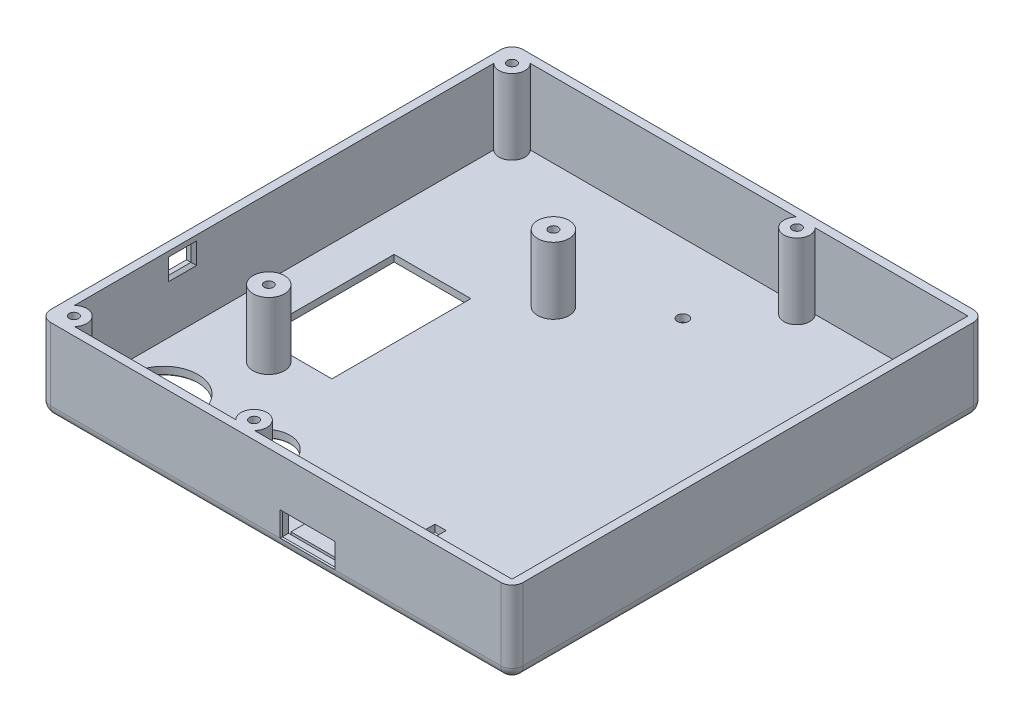
SolidWorks part; units mm, degrees
material "PLA"
ref_plane "前视基准面" through (0, 0, 0) normal (0, 0, 1) x (1, 0, 0)
ref_plane "上视基准面" through (0, 0, 0) normal (0, 1, 0) x (1, 0, 0)
ref_plane "右视基准面" through (0, 0, 0) normal (1, 0, 0) x (0, 0, -1)
sketch "草图1" plane through (0, 0, 0) normal (0, 1, 0) x (1, 0, 0)
  line L1 (-42.5, 42.5) -> (42.5, 42.5)
  line L2 (-42.5, 42.5) -> (-42.5, -42.5)
  line L3 (-42.5, -42.5) -> (42.5, -42.5)
  line L4 (42.5, 42.5) -> (42.5, -42.5)
  line L5 (-42.5, 42.5) -> (42.5, -42.5) construction
  line L6 (-42.5, -42.5) -> (42.5, 42.5) construction
  point P0 (0, 0)
  dimension "D1" = 85
  dimension "D2" = 85
extrude "凸台-拉伸1" add sketch "草图1" along normal blind 15
shell "抽壳1" thickness 1.5 removed face at (0, 15, 0)
fillet "圆角1" radius 2 4 edges at (0, 0, 42.5) (-42.5, 0, 0) (42.5, 0, 0) (0, 0, -42.5)
fillet "圆角2" radius 2 8 edges at (-41.9142, 0.5858, -41.9142) (-41.9142, 0.5858, 41.9142) (41.9142, 0.5858, 41.9142) (41.9142, 0.5858, -41.9142) (-42.5, 8.5, -42.5) (-42.5, 8.5, 42.5) (42.5, 8.5, 42.5) (42.5, 8.5, -42.5)
sketch "草图16" plane through (0, 0, 42.5) normal (0, 0, 1) x (1, 0, 0)
  line L1 (1, 2.25) -> (10.5, 2.25)
  line L2 (1, 2.25) -> (1, 6.25)
  line L3 (1, 6.25) -> (10.5, 6.25)
  line L4 (10.5, 2.25) -> (10.5, 6.25)
  line L7 (10.25, 3) -> (10.25, 7) construction
  line L8 (1.25, 3) -> (1.25, 7) construction
  line L9 (10.25, 6) -> (1.25, 6) construction
  line L10 (9.75, 2.5) -> (1.75, 2.5) construction
  dimension "D1" = 0.25
  dimension "D2" = 0.25
  dimension "D3" = 0.25
  dimension "D4" = 0.25
extrude "充电口切除-拉伸7" cut sketch "草图16" against normal up to next
sketch "草图3" plane through (0, 0, 0) normal (0, -1, 0) x (1, 0, 0)
  line L1 (12, 25.85) -> (14, 25.85)
  line L2 (12, 25.85) -> (12, 33.85)
  line L3 (12, 33.85) -> (14, 33.85)
  line L4 (14, 25.85) -> (14, 33.85)
  line L7 (13, 31.2) -> (13, 28.5) construction
  line L8 (12.5, 31.2) -> (13.5, 31.2) construction
  line L9 (13.5, 28.5) -> (12.5, 28.5) construction
  line L10 (13, 29.85) -> (11.5693, 29.85) construction
  dimension "D1" = 2
  dimension "D2" = 8
extrude "充电灯切除-拉伸2" cut sketch "草图3" against normal up to next
sketch "草图4" plane through (0, 0, 0) normal (0, -1, 0) x (1, 0, 0)
  circle A2 centre (-32.65, 30) radius 6.15
  circle A3 centre (-32.65, 30) radius 5.85 construction
  circle A4 centre (-32.65, 30) radius 5.85 construction
extrude "按钮切除-拉伸3" cut sketch "草图4" against normal up to next
chamfer "充电口灯倒角1" distance 0.2 angle 45 12 edges at (13, 0, 33.85) (14, 0, 29.85) (12, 0, 29.85) (13, 0, 25.85) (10.5, 4.25, 41) (5.75, 2.25, 41) (5.75, 6.25, 41) (1, 4.25, 41) (10.5, 4.25, 42.5) (5.75, 2.25, 42.5) (5.75, 6.25, 42.5) (1, 4.25, 42.5)
sketch "草图5" plane through (-42.5, 0, 0) normal (-1, 0, 0) x (0, 0, 1)
  line L1 (16.25, 13.57) -> (20.25, 13.57)
  line L2 (16.25, 13.57) -> (16.25, 10.73)
  line L3 (16.25, 10.73) -> (20.25, 10.73)
  line L4 (20.25, 13.57) -> (20.25, 10.73)
  line L5 (18.25, 12.57) -> (16.45, 12.57) construction
  line L6 (18.25, 10.93) -> (20.05, 10.93) construction
  line L8 (20.05, 10.93) -> (20.05, 12.57) construction
  line L9 (16.45, 12.57) -> (16.45, 10.93) construction
  dimension "D1" = 0.2
  dimension "D2" = 1
  dimension "D3" = 0.2
  dimension "D4" = 0.2
extrude "开关切除-拉伸4" cut sketch "草图5" against normal up to next
chamfer "开关倒角3" distance 0.2 angle 45 4 edges at (-42.5, 12.15, 20.25) (-42.5, 10.73, 18.25) (-42.5, 12.15, 16.25) (-42.5, 13.57, 18.25)
chamfer "开关倒角4" distance 0.5 angle 45 4 edges at (-41, 12.15, 20.25) (-41, 10.73, 18.25) (-41, 12.15, 16.25) (-41, 13.57, 18.25)
sketch "草图6" plane through (0, 0, 0) normal (0, -1, 0) x (1, 0, 0)
  line L5 (-19.9, 12.5) -> (-33.7, 12.5)
  line L6 (-33.7, 12.5) -> (-33.7, -12.5)
  line L7 (-19.9, -12.5) -> (-33.7, -12.5)
  line L8 (-19.9, 12.5) -> (-19.9, -12.5)
  line L9 (40.5, 40.5) -> (-40.5, 40.5) construction
  line L10 (-40.5, 40.5) -> (-40.5, -40.5) construction
  dimension "D1" = 13.8
  dimension "D2" = 25
  dimension "D3" = 28
  dimension "D4" = 6.8
extrude "屏幕切除-拉伸6" cut sketch "草图6" against normal up to next
chamfer "屏幕倒角6" distance 0.3 angle 45 4 edges at (-26.8, 0, 12.5) (-33.7, 0, 0) (-26.8, 0, -12.5) (-19.9, 0, 0)
sketch "草图7" plane through (0, 0, 0) normal (0, -1, 0) x (1, 0, 0)
  line L4 (40.5, 40.5) -> (-40.5, 40.5)
  line L6 (40.5, 40.5) -> (-40.5, 40.5)
  line L8 (-40.5, 40.5) -> (-40.5, -40.5)
  line L10 (-40.5, 40.5) -> (-40.5, -40.5)
  line L12 (-40.5, -40.5) -> (40.5, -40.5)
  line L13 (-40.5, -40.5) -> (40.5, -40.5)
  line L14 (40.5, -40.5) -> (40.5, 40.5)
  line L15 (40.5, -40.5) -> (40.5, 40.5)
  circle A0 centre (-14.8774, 29.5) radius 4.25 construction
  circle A1 centre (-14.8774, 29.5) radius 4.25 construction
  circle A3 centre (-14.8774, 29.5) radius 4.45
  dimension "D1" = 0
extrude "人体切除-拉伸7" cut sketch "草图7" against normal up to next contours A3
sketch "草图9" plane through (0, 0, 0) normal (0, -1, 0) x (1, 0, 0)
  circle A0 centre (2.2382, -28.5) radius 1
extrude "蜂鸣切除-拉伸8" cut sketch "草图9" against normal up to next
chamfer "蜂鸣倒角7" distance 0.2 angle 45 3 edges at (2.2382, 0, -29.5) (-32.65, 0, 23.85) (-14.8774, 0, 25.05)
sketch "草图10" plane through (0, 1.5, 0) normal (0, 1, 0) x (1, 0, 0)
  line L0 (41, 41) -> (-41, 41) construction
  line L1 (-41, 41) -> (-41, -41) construction
  line L2 (-41, -41) -> (41, -41) construction
  line L3 (8.85, 37.5) -> (8.85, 36.5) construction
  line L4 (-3, -41) -> (-3, -13) construction
  line L6 (-41, -41) -> (41, -41) construction
  circle A0 centre (-39.4, 39.4) radius 0.825
  circle A1 centre (-39.4, -39.4) radius 0.825
  circle A2 centre (-7, -39.4) radius 0.825
  circle A3 centre (11.85, 39.4) radius 0.825
  dimension "D1" = 1.65
  dimension "D6" = 3
  dimension "D2" = 1.6
  dimension "D3" = 1.6
  dimension "D4" = 1.6
  dimension "D5" = 1.6
  dimension "D7" = 1.6
  dimension "D8" = 4
  dimension "D9" = 1.6
extrude "四角固定拉伸-薄壁1" add sketch "草图10" along normal up to surface (13.5 mm away) thin thin type one direction wall 1.5
sketch "草图12" plane through (0, 1.5, 0) normal (0, 1, 0) x (1, 0, 0)
  line L1 (-12, -12.5) -> (-39, -12.5) construction
  line L2 (-24.75, -14.5) -> (-24.75, -19.5) construction
  circle A0 centre (-28.25, -15.5) radius 2.825
  circle A1 centre (-11.25, 18.7) radius 2.825
  circle A2 centre (-28.25, -15.5) radius 0.825
  circle A3 centre (-11.25, 18.7) radius 0.825
  circle A4 centre (-11.25, 18.7) radius 1 construction
  dimension "D1" = 2
  dimension "D4" = 2
  dimension "D7" = 1.65
  dimension "D8" = 1.65
  dimension "D2" = 3
  dimension "D3" = 3.5
extrude "压板固定凸台-拉伸2" add sketch "草图12" along normal up to surface (12 mm away)
sketch "草图14" plane through (42.5, 0, 0) normal (1, 0, 0) x (0, 0, -1)
  line L0 (40.5, 0) -> (-40.5, 0) construction
  line L1 (10, 0) -> (15, 0)
  line L2 (10, 0) -> (10, 5)
  line L3 (10, 5) -> (15, 5)
  line L4 (15, 0) -> (15, 5)
  line L5 (0, 0) -> (0, 15) construction
  line L6 (-40.5, 15) -> (40.5, 15) construction
  line L7 (-15, 0) -> (-15, 5)
  line L8 (-10, 5) -> (-15, 5)
  line L9 (-10, 0) -> (-10, 5)
  line L10 (-10, 0) -> (-15, 0)
  dimension "D1" = 5
  dimension "D2" = 5
  dimension "D3" = 10
extrude "电池顶凸台-拉伸3" add sketch "草图14" against normal blind 3.9 from surface starting at face at (41, 8.25, 0)
sketch "草图15" plane through (0, 1.5, 0) normal (0, 1, 0) x (1, 0, 0)
  line L1 (1.25, -41) -> (10.25, -41)
  line L2 (1.25, -41) -> (1.25, -37)
  line L3 (1.25, -37) -> (10.25, -37)
  line L4 (10.25, -41) -> (10.25, -37)
extrude "充电板凸台-拉伸4" add sketch "草图15" along normal up to surface (1 mm away)
